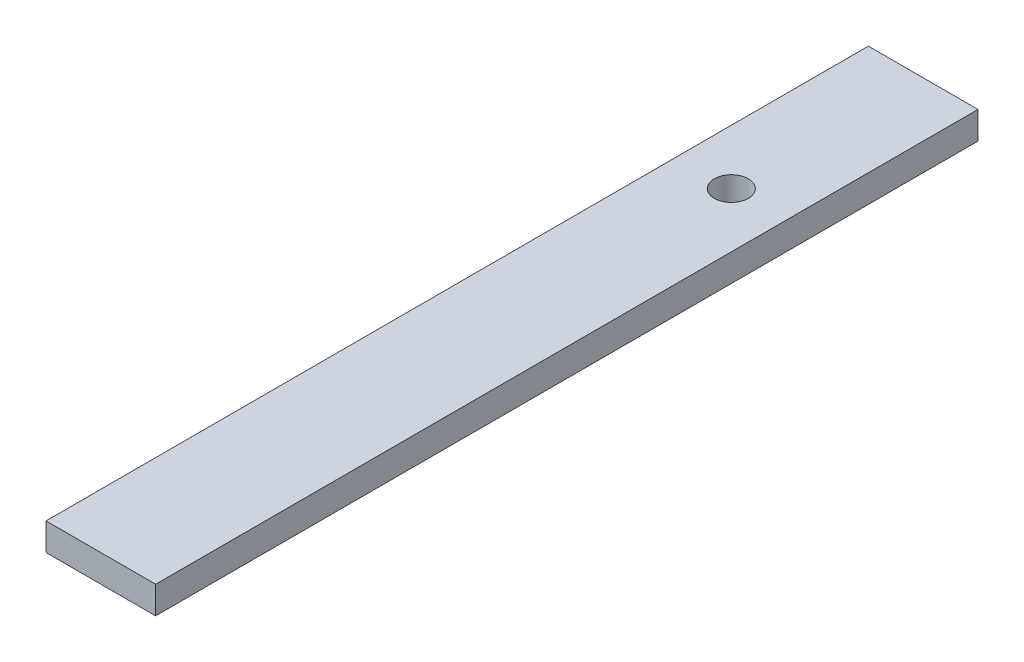
SolidWorks part; units mm, degrees
material "Maple"
ref_plane "Front Plane" through (0, 0, 0) normal (0, 0, 1) x (1, 0, 0)
ref_plane "Top Plane" through (0, 0, 0) normal (0, 1, 0) x (1, 0, 0)
ref_plane "Right Plane" through (0, 0, 0) normal (1, 0, 0) x (0, 0, -1)
sketch "Sketch1" plane through (0, 0, 0) normal (0, 1, 0) x (1, 0, 0)
  line L0 (0, 0) -> (50.8, 0)
  line L1 (0, 0) -> (0, 381)
  line L2 (50.8, 0) -> (50.8, 381)
  line L3 (0, 381) -> (50.8, 381)
  line L4 (25.4, 381) -> (25.4, 0) construction
  circle A0 centre (25.4, 292.1) radius 7.874
  dimension "D3" = 15.748
  dimension "D4" = 88.9
  dimension "D1" = 50.8
  dimension "D2" = 381
extrude "Boss-Extrude1" add sketch "Sketch1" along normal blind 12.7
ref_plane "Plane1" through (25.4, 0, 0) normal (-1, 0, 0) x (0, 0, 1)
